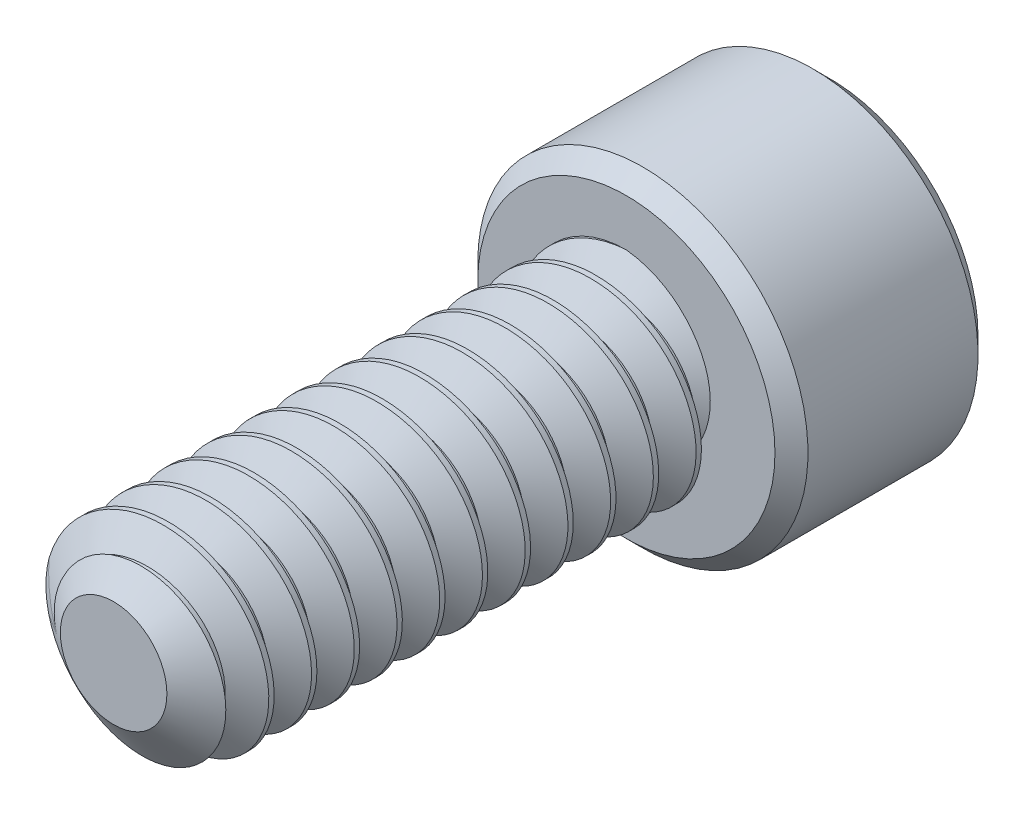
SolidWorks part; units mm, degrees
other "DetailItem1"
ref_plane "Front Plane" through (0, 0, 0) normal (0, 0, 1) x (1, 0, 0)
ref_plane "Top Plane" through (0, 0, 0) normal (0, 1, 0) x (1, 0, 0)
ref_plane "Right Plane" through (0, 0, 0) normal (1, 0, 0) x (0, 0, -1)
sketch "Sketch1" plane through (0, 0, 0) normal (0, 0, 1) x (1, 0, 0)
  circle A0 centre (0, 0) radius 1.2573
  dimension "OD" = 2.5146
extrude "Extrude1" add sketch "Sketch1" against normal blind 6.35
sketch "Sketch2" plane through (0, 0, 0) normal (0, 0, 1) x (1, 0, 0)
  circle A0 centre (0, 0) radius 1.2573 construction
  circle A1 centre (0, 0) radius 1.2573
curve "Helix/Spiral1" pitch 0.5292 height 6.8792 radius 1.2573 centre (0, 0, 0) axis (0, 0, -1) start towards (0, 1, 0) parameters "pitch"=0.5292
sketch "Sketch3" plane through (0, 0, 0) normal (1, 0, 0) x (0, 0, -1)
  line L0 (-0.463, 1.2573) -> (-0.2646, 0.9136)
  line L1 (-0.2646, 0.9136) -> (-0.1984, 0.9136)
  line L2 (-0.1984, 0.9136) -> (0, 1.2573)
  line L3 (-0.463, 1.2573) -> (0, 1.2573)
  line L4 (-0.2315, 1.2573) -> (-0.2315, 0.9136) construction
  line L5 (-0.3638, 1.0854) -> (-0.0992, 1.0854) construction
  line L6 (0, 1.2573) -> (0, -1.2573) construction
  dimension "D1" = 0.0661
  dimension "D2" = 0.2646
  dimension "D3" = 60
sweep "Cut-Sweep1" cut profiles "Sketch3" path "Helix/Spiral1"
sketch "Sketch4" plane through (0, 0, 0) normal (1, 0, 0) x (0, 0, -1)
  line L0 (0.4185, 1.2573) -> (0, 0.6596)
  line L1 (0, 0.6596) -> (0, 1.2573)
  line L2 (0.4185, 1.2573) -> (0, 1.2573)
  line L3 (-0.463, 1.2573) -> (0, 1.2573) construction
  line L4 (0, 0) -> (7.0209, 0) construction
  dimension "D1" = 55
  dimension "D2" = 0.254
revolve "Cut-Revolve1" cut sketch "Sketch4" angle 360 about L4
sketch "Sketch5" plane through (0, 0, 0) normal (1, 0, 0) x (0, 0, -1)
  line L0 (6.35, -0.9237) -> (6.35, 0.8971) construction
  line L1 (6.35, 1.3843) -> (0.1202, 1.3843)
  line L2 (6.35, 1.3843) -> (6.35, 0)
  line L3 (6.35, 0) -> (0, 0)
  line L4 (0, 1.0541) -> (0, 0)
  line L5 (0.1202, 1.3843) -> (0, 1.0541)
  line L6 (0, 0) -> (9.9695, 0) construction
  point P3 (0, 1.3843)
  point P10 (0, 1.3843)
  dimension "D1" = 0.3302
  dimension "D2" = 0.127
  dimension "D3" = 20
  dimension "Min Thread" = 0
revolve "partially thread" [suppressed] add sketch "Sketch5" angle 360 about L6
sketch "Sketch6" plane through (0, 0, -6.35) normal (0, 0, -1) x (-1, 0, 0)
  circle A0 centre (0, 0) radius 2.0447
  dimension "head dia" = 4.0894
extrude "Extrude2" add sketch "Sketch6" along normal blind 2.5146
sketch "Sketch7" plane through (0, 0, -8.8646) normal (0, 0, -1) x (-1, 0, 0)
  line L1 (0, 1.1457) -> (-0.9922, 0.5728)
  line L2 (-0.9922, 0.5728) -> (-0.9922, -0.5728)
  line L3 (-0.9922, -0.5728) -> (0, -1.1457)
  line L4 (0, -1.1457) -> (0.9922, -0.5728)
  line L5 (0.9922, -0.5728) -> (0.9922, 0.5728)
  line L6 (0.9922, 0.5728) -> (0, 1.1457)
  circle A0 centre (0, 0) radius 0.9922 construction
  dimension "hex dia" = 1.9844
extrude "Cut-Extrude1" cut sketch "Sketch7" against normal blind 1.4883
sketch "Sketch8" plane through (0, 0, -8.8646) normal (0, 0, -1) x (-1, 0, 0)
  circle A0 centre (0, 0) radius 1.1457
extrude "Cut-Extrude2" cut sketch "Sketch8" against normal through all draft 45
chamfer "Chamfer1" distance 0.2045 angle 45 2 edges at (-2.0447, 0, -8.8646) (-2.0447, 0, -6.35)
sketch "Sketch9" plane through (0, 0, 0) normal (1, 0, 0) x (0, 0, -1)
  line L0 (0, 1.2573) -> (0, -1.2573) construction
  line L1 (1.3229, 1.2573) -> (1.3229, -1.2573) construction
  dimension "D1" = 1.3229
  dimension "D4" = 0.635
  dimension "D5" = 0.3302
equation "\"D3@Helix/Spiral1\" = \"screw length@Extrude1\"+\"pitch@Helix/Spiral1\""
equation "\"D1@Sketch3\" = \"pitch@Helix/Spiral1\"*.125"
equation "\"D2@Sketch3\" = \"pitch@Helix/Spiral1\"*.5"
equation "\"D1@Cut-Extrude1\" = \"hex dia@Sketch7\"*.75"
equation "\"D1@Chamfer1\" = \"head dia@Sketch6\"*.05"
equation "\"D1@Sketch9\" = \"pitch@Helix/Spiral1\"*2.5"
